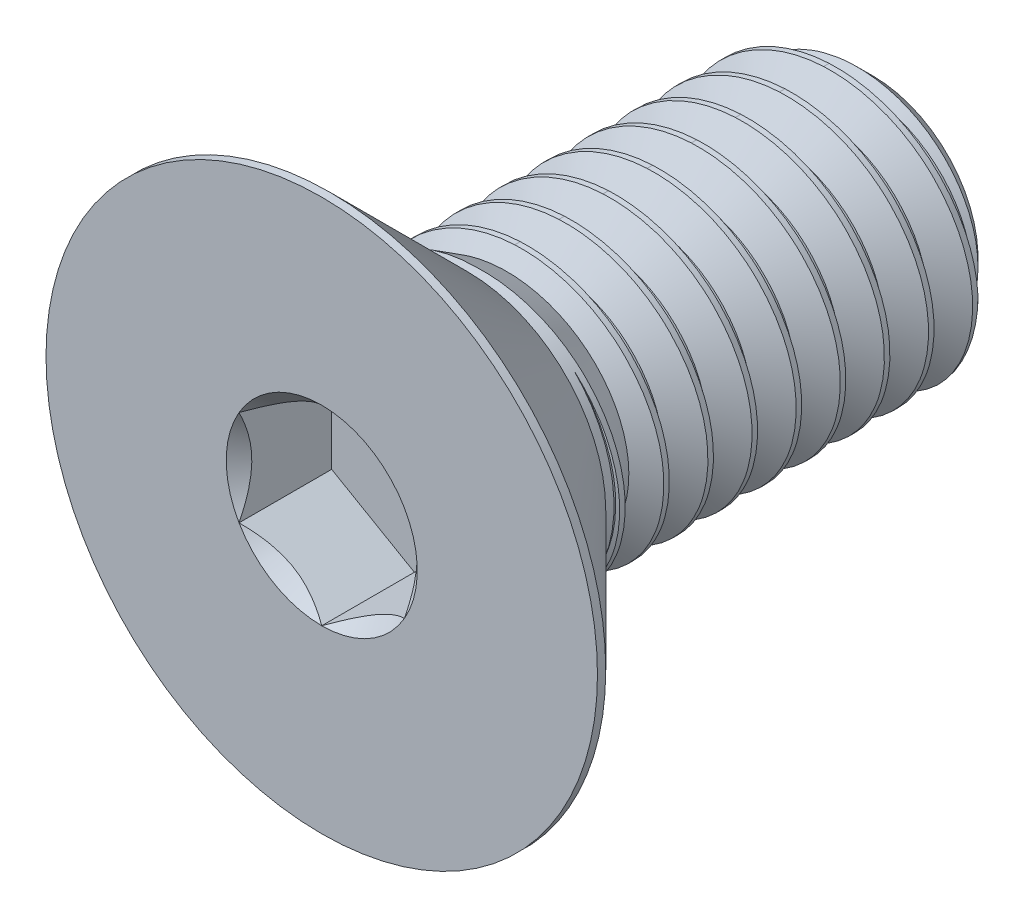
SolidWorks part; units mm, degrees
ref_plane "Front" through (0, 0, 0) normal (0, 0, 1) x (1, 0, 0)
ref_plane "Top" through (0, 0, 0) normal (0, 1, 0) x (1, 0, 0)
ref_plane "Right" through (0, 0, 0) normal (1, 0, 0) x (0, 0, -1)
sketch "Sketch1" plane through (0, 0, 0) normal (0, 0, 1) x (1, 0, 0)
  line L1 (1.5, 0.866) -> (0, 1.7321)
  line L8 (0, 1.7321) -> (-1.5, 0.866)
  line L9 (-1.5, 0.866) -> (-1.5, -0.866)
  line L10 (-1.5, -0.866) -> (0, -1.7321)
  line L11 (0, -1.7321) -> (1.5, -0.866)
  line L12 (1.5, -0.866) -> (1.5, 0.866)
  circle A0 centre (0, 0) radius 1.5 construction
  circle A1 centre (0, 0) radius 5
  point P7 (0, 5)
  dimension "Head Dia" = 10
  dimension "Hex" = 3
sketch "Sketch2" plane through (0, 0, 0) normal (1, 0, 0) x (0, 0, -1)
  line L2 (0, 0) -> (7.2, 0) construction
  line L3 (7.2, 0) -> (7.2, 2.5)
  line L6 (7.2, 2.5) -> (0, 2.5)
  line L8 (0, 2.5) -> (-0.15, 2.5)
  line L9 (-0.15, 2.5) -> (-2.65, 5)
  line L11 (-2.65, 5) -> (-2.8, 5)
  line L13 (-2.8, 5) -> (-2.8, 0)
  line L14 (-2.8, 0) -> (0, 0) construction
  line L15 (7.15, 2.5866) -> (7.55, 1.8938) construction
  line L16 (7.55, 1.8938) -> (7.95, 2.5866) construction
  line L17 (7.95, 2.5866) -> (7.15, 2.5866) construction
  line L18 (7.175, 2.5433) -> (7.925, 2.5433)
  line L19 (7.925, 2.5433) -> (7.6, 1.9804)
  line L20 (7.6, 1.9804) -> (7.5, 1.9804)
  line L21 (7.5, 1.9804) -> (7.175, 2.5433)
  line L22 (7.55, 1.9804) -> (7.55, 1.8938) construction
  line L23 (7.2, 2.5) -> (7.9, 2.5) construction
  line L24 (7.55, 2.5866) -> (7.55, 2.5) construction
  line L25 (7.2, 1.9) -> (6.6, 2.5)
  line L26 (7.2, -2.5) -> (0, -2.5)
  point P28 (7.55, 2.5433)
  point P32 (6, -2.5)
  point P33 (-1.12, 0)
  point P35 (-2.8, 5)
  dimension "Dia" = 5
  dimension "Head Ht" = 2.8
  dimension "D2" = 45
  dimension "Lg" = 10
  dimension "Pitch" = 0.8
  dimension "D3" = 0.1
  dimension "D1" = 45
  dimension "D4" = 0.6
  dimension "D5" = 1.2
  dimension "D6" = 1.68
sketch "Sketch7" plane through (0, 0, 0) normal (1, 0, 0) x (0, 0, -1)
  line L2 (-2.8, 0) -> (-2.8, 5)
  line L3 (-2.8, 5) -> (-2.65, 5)
  line L5 (-2.65, 5) -> (-0.15, 2.5)
  line L6 (-0.15, 2.5) -> (6.6, 2.5)
  line L8 (6.6, 2.5) -> (7.2, 1.9)
  line L9 (7.2, 1.9) -> (7.2, 0)
  line L11 (7.2, 0) -> (-2.8, 0)
revolve "Revolve2" add sketch "Sketch7" angle 360 mid plane about L11
sketch "Sketch5" plane through (0, 0, 2.8) normal (0, 0, 1) x (1, 0, 0)
  line L0 (1.5, -0.866) -> (1.5, 0.866) construction
  line L1 (0, -1.7321) -> (1.5, -0.866) construction
  line L2 (-1.5, -0.866) -> (0, -1.7321) construction
  line L3 (-1.5, 0.866) -> (-1.5, -0.866) construction
  line L4 (0, 1.7321) -> (-1.5, 0.866) construction
  line L5 (1.5, 0.866) -> (0, 1.7321) construction
  line L6 (1.5, -0.866) -> (1.5, 0.866)
  line L7 (0, -1.7321) -> (1.5, -0.866)
  line L8 (-1.5, -0.866) -> (0, -1.7321)
  line L9 (-1.5, 0.866) -> (-1.5, -0.866)
  line L10 (0, 1.7321) -> (-1.5, 0.866)
  line L11 (1.5, 0.866) -> (0, 1.7321)
extrude "Cut-Extrude2" cut sketch "Sketch5" against normal up to vertex (1.68 mm away) up to point (0, 0, 1.12)
sketch "Sketch6" plane through (0, 0, 2.8) normal (0, 0, 1) x (1, 0, 0)
  circle A0 centre (0, 0) radius 1.7321
extrude "Cut-Extrude3" cut sketch "Sketch6" against normal up to vertex (1.68 mm away) draft 45 up to point (0, 0, 1.12)
sketch "Sketch3" plane through (0, 0, -7.2) normal (0, 0, -1) x (-1, 0, 0)
  circle A0 centre (0, 0) radius 2.5
split "Split1" trim tools "Front" bodies to split 113 resulting bodies 125 126
curve "Helix/Spiral1" pitch 0.8 height 8 turns 10
sketch "Sketch8" plane through (0, 0, 0) normal (1, 0, 0) x (0, 0, -1)
  line L0 (7.175, 2.5433) -> (7.925, 2.5433) construction
  line L1 (7.5, 1.9804) -> (7.175, 2.5433) construction
  line L2 (7.6, 1.9804) -> (7.5, 1.9804) construction
  line L3 (7.925, 2.5433) -> (7.6, 1.9804) construction
  line L4 (7.175, 2.5433) -> (7.925, 2.5433)
  line L5 (7.5, 1.9804) -> (7.175, 2.5433)
  line L6 (7.6, 1.9804) -> (7.5, 1.9804)
  line L7 (7.925, 2.5433) -> (7.6, 1.9804)
sweep "Cut-Sweep1" cut profiles "Sketch8" path "Helix/Spiral1" align with end faces yes
sketch "Sketch9" plane through (0, 0, 0) normal (0, 0, 1) x (1, 0, 0)
  circle A0 centre (0, 0) radius 2.5
extrude "Boss-Extrude1" add sketch "Sketch9" against normal up to vertex (7.2 mm away) draft 30.9 up to point (0, 0, -7.2)
equation "\"D3@Helix/Spiral1\" =  ( \"Lg@Sketch2\" - \"Head Ht@Sketch2\" )  + \"Pitch@Sketch2\""
equation "\"D1\"= \"Head Ht@Sketch2\" * .7"
equation "\"D1\"= \"D1\""
equation "\"D4@Helix/Spiral1\" = \"Pitch@Sketch2\""
equation "\"D3@Sketch2\" = \"Pitch@Sketch2\" / 8"
equation "\"D4@Sketch2\" = \"Pitch@Sketch2\" * 0.75"
equation "\"D5@Sketch2\" = \"Pitch@Sketch2\" * 1.5"
equation "\"D6@Sketch2\" = \"Head Ht@Sketch2\" * 0.6"
